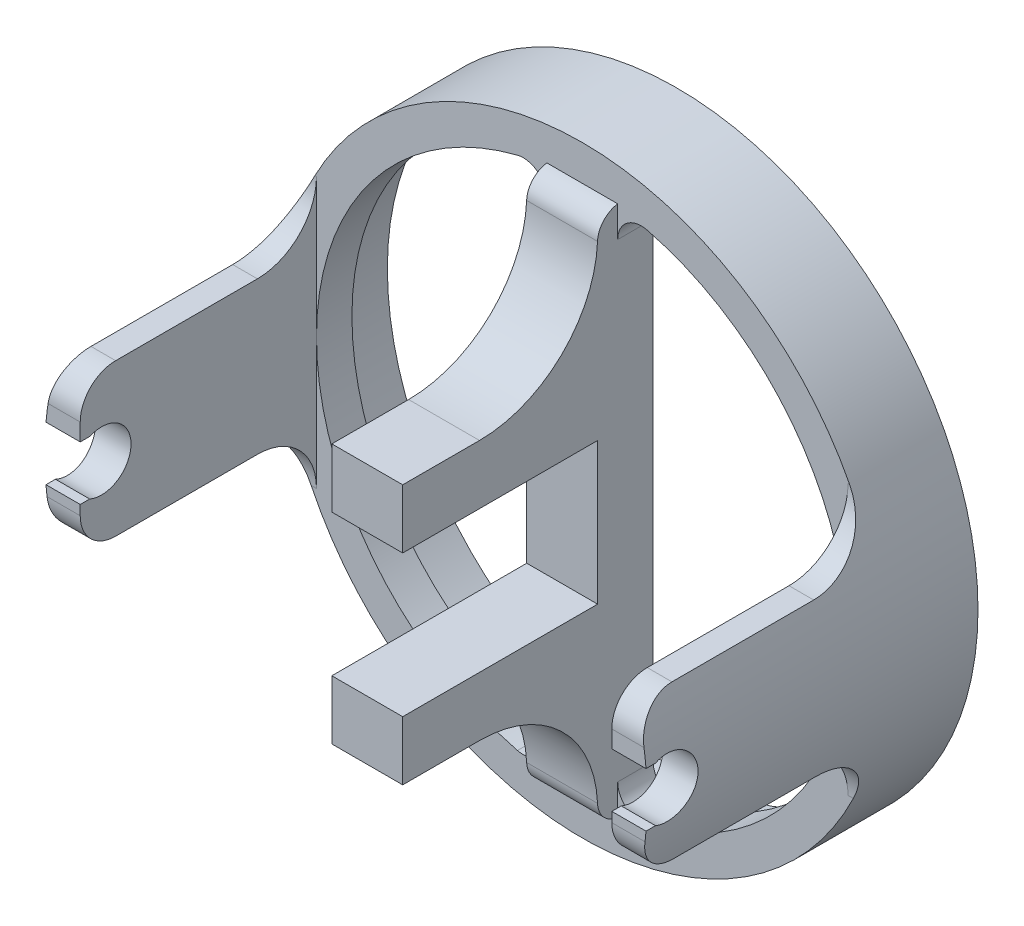
SolidWorks part; units mm, degrees
ref_plane "Alzado" through (0, 0, 0) normal (0, 0, 1) x (1, 0, 0)
ref_plane "Planta" through (0, 0, 0) normal (0, 1, 0) x (1, 0, 0)
ref_plane "Vista lateral" through (0, 0, 0) normal (1, 0, 0) x (0, 0, -1)
sketch "Croquis1" plane through (0, 0, 0) normal (0, 0, 1) x (1, 0, 0)
  circle A0 centre (0, 0) radius 25.5
  circle A1 centre (0, 0) radius 22.5
  dimension "D1" = 51
  dimension "D2" = 3
extrude "Saliente-Extruir1" add sketch "Croquis1" along normal blind 8
sketch "Croquis2" plane through (0, 0, 0) normal (0, 0, -1) x (-1, 0, 0)
  circle A0 centre (0, 0) radius 24.5
  dimension "D1" = 49
extrude "Cortar-Extruir1" cut sketch "Croquis2" against normal blind 5
sketch "Croquis3" plane through (0, 0, 8) normal (0, 0, 1) x (1, 0, 0)
  line L0 (0, -22.5) -> (0, 22.5) construction
  line L1 (-3, 22.5) -> (3, 22.5)
  line L2 (-3, 22.5) -> (-3, -22.5)
  line L3 (-3, -22.5) -> (3, -22.5)
  line L4 (3, 22.5) -> (3, -22.5)
  circle A1 centre (0, 0) radius 22.5 construction
  point P6 (0, 22.5)
  dimension "D1" = 6
extrude "Saliente-Extruir2" add sketch "Croquis3" against normal blind 3 and the other way blind 1.7
sketch "Croquis4" plane through (0, 0, 9.7) normal (0, 0, 1) x (1, 0, 0)
  line L0 (3, 0) -> (-3, 0) construction
  line L1 (3, -22.5) -> (3, 22.5) construction
  line L2 (-3, 22.5) -> (-3, -22.5) construction
  line L3 (3, 6) -> (3, 11)
  line L4 (-3, -6) -> (3, -6)
  line L5 (-3, -6) -> (-3, -11)
  line L6 (-3, -11) -> (3, -11)
  line L7 (3, -6) -> (3, -11)
  line L8 (-3, 11) -> (3, 11)
  line L9 (-3, 6) -> (-3, 11)
  line L10 (-3, 6) -> (3, 6)
  dimension "D1" = 6
  dimension "D2" = 5
extrude "Saliente-Extruir3" add sketch "Croquis4" along normal blind 16.5
fillet "Redondeo1" radius 10 2 edges at (0, -11, 9.7) (0, 11, 9.7)
sketch "Croquis5" plane through (0, 0, 8) normal (0, 0, 1) x (1, 0, 0)
  line L0 (0, 0) -> (25.5, 0) construction
  line L1 (-24.7547, -6.12) -> (-22.5, -6.12) construction
  line L2 (-25.5, -6) -> (-25.5, 6) construction
  line L3 (-24.5904, 6.75) -> (-22.5, 6.75) construction
  line L4 (25.5, -6) -> (25.5, 6) construction
  line L5 (-22.5, -6.12) -> (-24.7547, -6.12)
  line L6 (-24.5904, 6.75) -> (-22.5, 6.75)
  line L7 (24.5904, 6.75) -> (22.5, 6.75)
  line L8 (24.7547, -6.12) -> (22.5, -6.12)
  line L9 (22.5, -6.12) -> (22.5, 6.75)
  line L10 (0, 0) -> (0, 6.45) construction
  line L11 (-22.5, -6.12) -> (-22.5, 6.75)
  line L12 (22.5, -6.12) -> (24.7547, -6.12) construction
  line L13 (22.5, 6.75) -> (24.5904, 6.75) construction
  line L14 (-21.4636, 6.75) -> (20.5097, 6.75) construction
  line L15 (-21.6517, -6.12) -> (21.6517, -6.12) construction
  circle A0 centre (0, 0) radius 25.5 construction
  arc A1 (-24.5904, 6.75) -> (-24.7547, -6.12) centre (0, 0) ccw
  arc A2 (-21.4636, 6.75) -> (-21.6517, -6.12) centre (0, 0) ccw construction
  arc A3 (-3, 22.2991) -> (-3, -22.2991) centre (0, 0) ccw construction
  arc A4 (24.7547, -6.12) -> (24.5904, 6.75) centre (0, 0) ccw
  arc A5 (21.6517, -6.12) -> (22.5, 0) centre (0, 0) ccw construction
  dimension "D1" = 12
extrude "Saliente-Extruir4" add sketch "Croquis5" along normal blind 20
sketch "Croquis6" plane through (0, 0, 0) normal (1, 0, 0) x (0, 0, -1)
  line L0 (-27.2, -2.2913) -> (-27.2, 2.2913) construction
  line L1 (-27.2, 2.2913) -> (-29.1515, 2.2913)
  line L2 (-29.1515, 2.2913) -> (-29.1515, -2.2913)
  line L3 (-29.1515, -2.2913) -> (-27.2, -2.2913)
  line L4 (-9.7, -6) -> (-9.7, 6) construction
  arc A0 (-27.2, -2.2913) -> (-27.2, 2.2913) centre (-26.2, 0) ccw
  dimension "D2" = 5
  dimension "D1" = 16.5
  dimension "D3" = 1
extrude "Cortar-Extruir2" cut sketch "Croquis6" against normal through all and the other way through all
fillet "Redondeo2" radius 5 4 edges at (-23.5452, 6.75, 8) (-23.6274, -6.12, 8) (23.6274, -6.12, 8) (23.5452, 6.75, 8)
fillet "Redondeo3" radius 3 4 edges at (23.5452, 6.75, 28) (23.6274, -6.12, 28) (-23.5452, 6.75, 28) (-23.6274, -6.12, 28)
fillet "Redondeo4" radius 2 2 edges at (0, -22.5, 9.7) (0, 22.5, 9.7)
fillet "Redondeo5" radius 2 4 edges at (3, 22.2991, 6.5) (3, -22.2991, 6.5) (-3, 22.2991, 6.5) (-3, -22.2991, 6.5)
